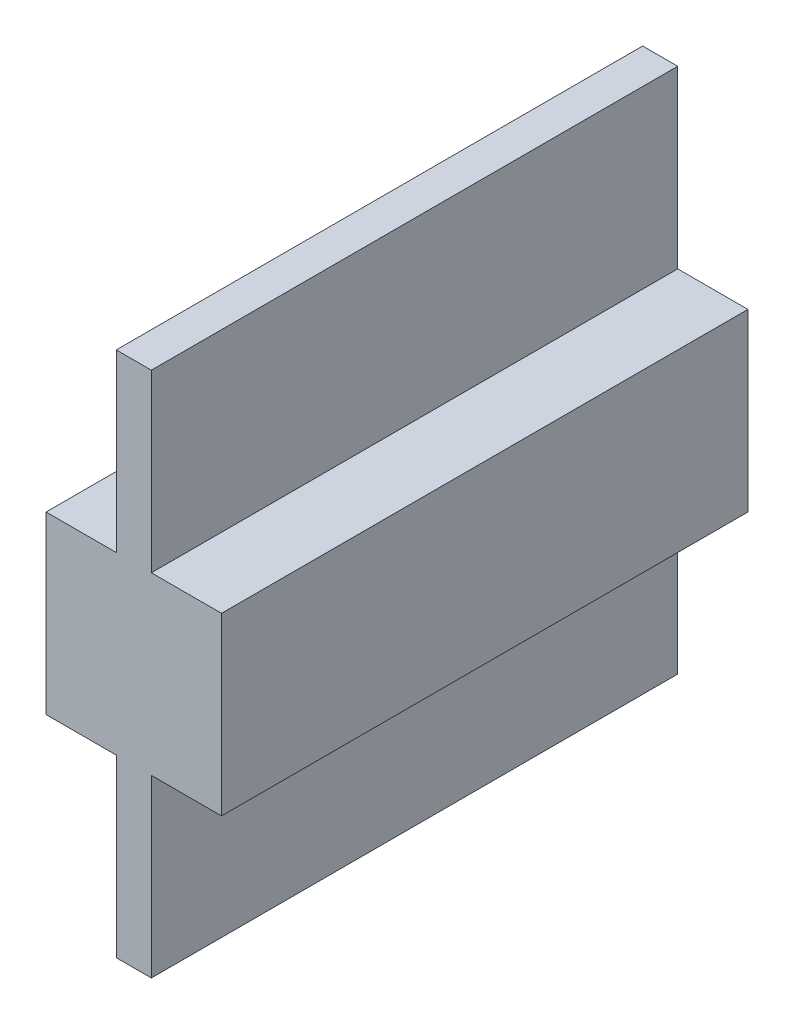
SolidWorks part; units mm, degrees
material "7050-T73510"
ref_plane "Front Plane" through (0, 0, 0) normal (0, 0, 1) x (1, 0, 0)
ref_plane "Top Plane" through (0, 0, 0) normal (0, 1, 0) x (1, 0, 0)
ref_plane "Right Plane" through (0, 0, 0) normal (1, 0, 0) x (0, 0, -1)
sketch "Sketch3" plane through (0, 0, 0) normal (1, 0, 0) x (0, 0, -1)
  line L1 (150, 50) -> (150, -50)
  line L2 (150, 50) -> (-150, 50)
  line L3 (-150, 50) -> (-150, -50)
  line L4 (150, -50) -> (-150, -50)
  line L5 (150, 50) -> (150, 150)
  line L6 (150, 50) -> (-150, 50)
  line L7 (-150, 50) -> (-150, 150)
  line L8 (150, 150) -> (-150, 150)
  line L9 (150, -50) -> (150, -150)
  line L10 (150, -50) -> (-150, -50)
  line L11 (-150, -50) -> (-150, -150)
  line L12 (150, -150) -> (-150, -150)
  dimension "D1" = 300
  dimension "D2" = 100
  dimension "D3" = 50
  dimension "D4" = 150
  dimension "D5" = 100
  dimension "D6" = 100
extrude "Boss-Extrude3" add sketch "Sketch3" along normal mid plane 100 contours L4 L1 L2 L3 region at (0, 0, 0)
extrude "Boss-Extrude4" add sketch "Sketch3<4>" along normal mid plane 20 contours L5 L8 L7 L2 | L12 L9 L4 L11 region at (0, 100, 0) region at (0, -100, 0)
sketch "Sketch3<4>" plane through (0, 0, 0) normal (1, 0, 0) x (0, 0, -1) same geometry as "Sketch3"
